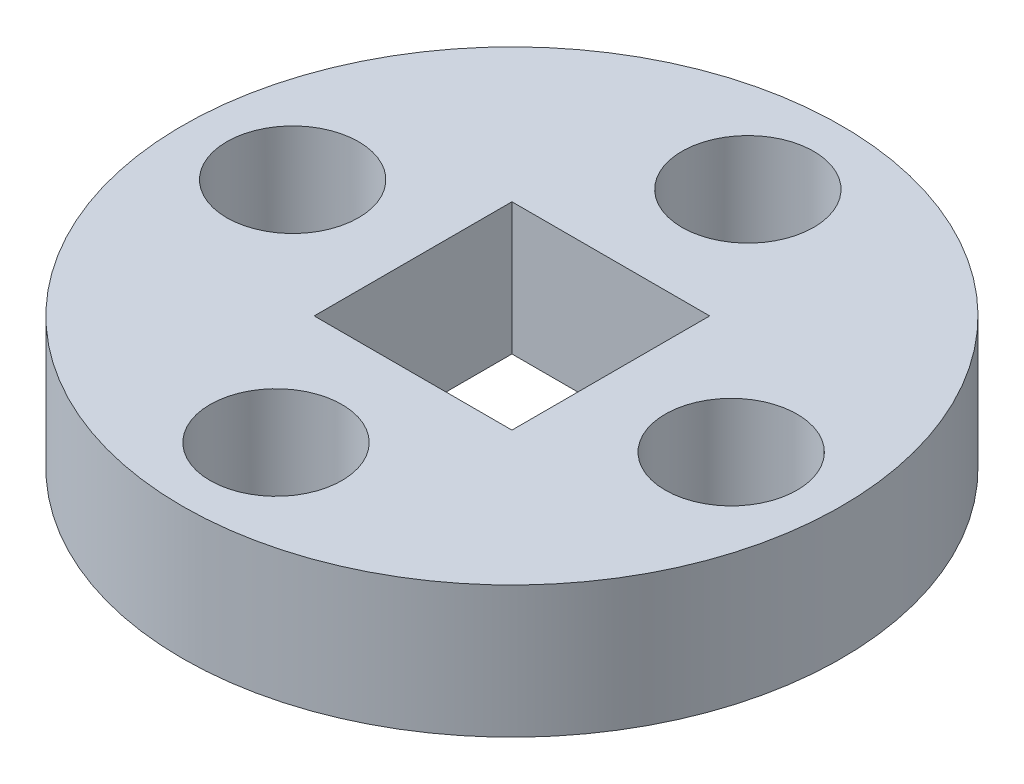
SolidWorks part; units mm, degrees
ref_plane "Ebene vorne" through (0, 0, 0) normal (0, 0, 1) x (1, 0, 0)
ref_plane "Ebene oben" through (0, 0, 0) normal (0, 1, 0) x (1, 0, 0)
ref_plane "Ebene rechts" through (0, 0, 0) normal (1, 0, 0) x (0, 0, -1)
sketch "Skizze1" plane through (0, 0, 0) normal (0, 1, 0) x (1, 0, 0)
  circle A0 centre (0, 0) radius 5
extrude "Aufsatz-Linear austragen1" add sketch "Skizze1" along normal blind 2
sketch "Skizze3" plane through (0, 2, 0) normal (0, 1, 0) x (1, 0, 0)
  line L0 (1.5, 1.5) -> (-1.5, 1.5)
  line L1 (1.5, 1.5) -> (1.5, -1.5)
  line L2 (1.5, -1.5) -> (-1.5, -1.5)
  line L3 (-1.5, 1.5) -> (-1.5, -1.5)
  line L4 (0, 0) -> (0, -3) construction
  line L5 (0, 0) -> (-10.1495, 0) construction
  point P8 (-1.5, 0)
  point P9 (0, -1.5)
extrude "Schnitt-Linear austragen1" cut sketch "Skizze3" against normal blind 3
sketch "Skizze4" plane through (0, 2, 0) normal (0, 1, 0) x (1, 0, 0)
  circle A0 centre (3.4528, -0.1264) radius 1
extrude "Schnitt-Linear austragen2" cut sketch "Skizze4" against normal blind 3
pattern_circular "Kreismuster1" count 4 over 360 about axis through (0, 2, 0) along (0, -1, 0) of "Schnitt-Linear austragen2"
